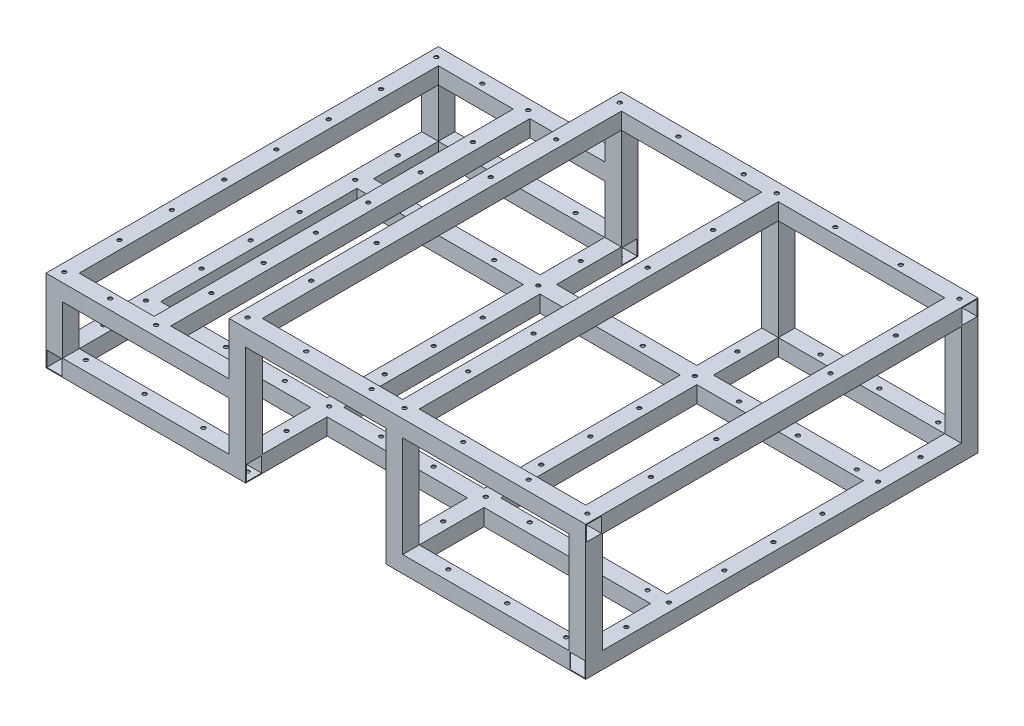
SolidWorks part; units mm, degrees
ref_plane "Front Plane" through (0, 0, 0) normal (0, 0, 1) x (1, 0, 0)
ref_plane "Top Plane" through (0, 0, 0) normal (0, 1, 0) x (1, 0, 0)
ref_plane "Right Plane" through (0, 0, 0) normal (1, 0, 0) x (0, 0, -1)
sketch "Sketch1" plane through (0, 0, 0) normal (0, 1, 0) x (1, 0, 0)
  line L0 (0, 0) -> (-415.7612, 0) construction
  line L1 (-387.3, -150) -> (387.3, -150)
  line L2 (-387.3, -150) -> (-387.3, -175.4)
  line L3 (-387.3, -175.4) -> (387.3, -175.4)
  line L4 (387.3, -150) -> (387.3, -175.4)
  line L9 (0, 0) -> (0, -321.173) construction
  line L10 (387.3, 150) -> (387.3, 175.4)
  line L11 (-387.3, 175.4) -> (387.3, 175.4)
  line L12 (-387.3, 150) -> (-387.3, 175.4)
  line L13 (-387.3, 150) -> (387.3, 150)
  point P7 (0, -175.4)
  dimension "D1" = 774.6
  dimension "D2" = 25.4
  dimension "D3" = 150
  dimension "D4" = 0
extrude "Boss-Extrude1" add sketch "Sketch1" along normal blind 25.4
sketch "Sketch4" plane through (-387.3, 0, 0) normal (-1, 0, 0) x (0, 0, 1)
  line L0 (-175.4, 25.4) -> (-150, 25.4) construction
  line L1 (-174.2, 24.2) -> (-151.2, 24.2)
  line L2 (-174.2, 24.2) -> (-174.2, 1.2)
  line L3 (-174.2, 1.2) -> (-151.2, 1.2)
  line L4 (-151.2, 24.2) -> (-151.2, 1.2)
  line L5 (-150, 25.4) -> (-150, 0) construction
  line L6 (-175.4, 0) -> (-150, 0) construction
  line L7 (-175.4, 25.4) -> (-175.4, 0) construction
  line L8 (0, 0) -> (0, 21.4103) construction
  line L9 (174.2, 1.2) -> (151.2, 1.2)
  line L10 (151.2, 24.2) -> (151.2, 1.2)
  line L11 (174.2, 24.2) -> (151.2, 24.2)
  line L12 (174.2, 24.2) -> (174.2, 1.2)
  dimension "D1" = 1.2
  dimension "D2" = 1.2
  dimension "D3" = 1.2
  dimension "D4" = 1.2
extrude "Cut-Extrude2" cut sketch "Sketch4" against normal up to next (774.6 mm away)
sketch "Sketch2" plane through (0, 0, 0) normal (0, -1, 0) x (1, 0, 0)
  line L0 (0, 0) -> (0, -349.2287) construction
  line L1 (412.7, 300) -> (387.3, 300)
  line L2 (412.7, 300) -> (412.7, -300)
  line L3 (412.7, -300) -> (387.3, -300)
  line L4 (387.3, 300) -> (387.3, -300)
  line L5 (0, 0) -> (432.1136, 0) construction
  line L6 (387.3, -150) -> (387.3, -175.4) construction
  line L7 (-387.3, 300) -> (-387.3, -300)
  line L8 (-412.7, -300) -> (-387.3, -300)
  line L9 (-412.7, 300) -> (-412.7, -300)
  line L10 (-412.7, 300) -> (-387.3, 300)
  point P10 (387.3, 0)
  dimension "D1" = 25.4
  dimension "D2" = 600
  dimension "D3" = 25.4
  dimension "D4" = 0
extrude "Boss-Extrude2" add sketch "Sketch2" against normal blind 25.4
sketch "Sketch3" plane through (0, 0, -300) normal (0, 0, -1) x (-1, 0, 0)
  line L0 (-387.3, 25.4) -> (-412.7, 25.4) construction
  line L1 (-411.5, 24.2) -> (-388.5, 24.2)
  line L2 (-411.5, 24.2) -> (-411.5, 1.2)
  line L3 (-411.5, 1.2) -> (-388.5, 1.2)
  line L4 (-388.5, 24.2) -> (-388.5, 1.2)
  line L5 (-387.3, 25.4) -> (-387.3, 0) construction
  line L6 (-387.3, 0) -> (-412.7, 0) construction
  line L7 (-412.7, 25.4) -> (-412.7, 0) construction
  line L8 (0, 0) -> (0, 119.739) construction
  line L9 (388.5, 24.2) -> (388.5, 1.2)
  line L10 (411.5, 1.2) -> (388.5, 1.2)
  line L11 (411.5, 24.2) -> (411.5, 1.2)
  line L12 (411.5, 24.2) -> (388.5, 24.2)
  point P10 (-400, 0)
  dimension "D1" = 1.2
  dimension "D2" = 1.2
  dimension "D3" = 1.2
  dimension "D4" = 1.2
extrude "Cut-Extrude1" cut sketch "Sketch3" against normal up to next
sketch "Sketch6" plane through (-387.3, 0, 0) normal (1, 0, 0) x (0, 0, -1)
  line L0 (300, 0) -> (175.4, 0) construction
  line L1 (300, 25.4) -> (274.6, 25.4)
  line L2 (300, 25.4) -> (300, 0)
  line L3 (300, 0) -> (274.6, 0)
  line L4 (274.6, 25.4) -> (274.6, 0)
  line L5 (0, 0) -> (0, 25.4) construction
  line L6 (150, 0) -> (-150, 0) construction
  line L7 (150, 25.4) -> (-150, 25.4) construction
  line L13 (-274.6, 25.4) -> (-274.6, 0)
  line L14 (-300, 0) -> (-274.6, 0)
  line L15 (-300, 25.4) -> (-300, 0)
  line L16 (-300, 25.4) -> (-274.6, 25.4)
  dimension "D1" = 25.4
extrude "Boss-Extrude3" add sketch "Sketch6" along normal blind 280
sketch "Sketch7" plane through (387.3, 0, 0) normal (-1, 0, 0) x (0, 0, 1)
  line L0 (-175.4, 25.4) -> (-300, 25.4) construction
  line L1 (-300, 0) -> (-274.6, 0)
  line L2 (-300, 0) -> (-300, 25.4)
  line L3 (-300, 25.4) -> (-274.6, 25.4)
  line L4 (-274.6, 0) -> (-274.6, 25.4)
  line L10 (0, 0) -> (0, 25.4) construction
  line L11 (150, 0) -> (-150, 0) construction
  line L12 (150, 25.4) -> (-150, 25.4) construction
  line L13 (274.6, 0) -> (274.6, 25.4)
  line L14 (300, 25.4) -> (274.6, 25.4)
  line L15 (300, 0) -> (300, 25.4)
  line L16 (300, 0) -> (274.6, 0)
  dimension "D1" = 25.4
extrude "Boss-Extrude4" add sketch "Sketch7" along normal blind 280
ref_plane "Plane1" through (0, 0, 0) normal (1, 0, 0) x (0, 0, -1)
sketch "Sketch8" plane through (0, 0, 0) normal (1, 0, 0) x (0, 0, -1)
  line L4 (-275.8, 24.2) -> (-298.8, 24.2)
  line L5 (-298.8, 24.2) -> (-298.8, 1.2)
  line L6 (-298.8, 1.2) -> (-275.8, 1.2)
  line L7 (-275.8, 1.2) -> (-275.8, 24.2)
  line L8 (-274.6, 25.4) -> (-300, 25.4)
  line L9 (-300, 25.4) -> (-300, 0)
  line L10 (-300, 0) -> (-274.6, 0)
  line L11 (-274.6, 0) -> (-274.6, 25.4)
  line L12 (-274.6, 25.4) -> (-300, 25.4)
  line L13 (-300, 25.4) -> (-300, 0)
  line L14 (-300, 0) -> (-274.6, 0)
  line L15 (-274.6, 0) -> (-274.6, 25.4)
  line L16 (300, 0) -> (300, 25.4)
  line L17 (300, 25.4) -> (274.6, 25.4)
  line L18 (274.6, 25.4) -> (274.6, 0)
  line L19 (274.6, 0) -> (300, 0)
  line L20 (300, 0) -> (300, 25.4)
  line L21 (300, 25.4) -> (274.6, 25.4)
  line L22 (274.6, 25.4) -> (274.6, 0)
  line L23 (274.6, 0) -> (300, 0)
  line L24 (298.8, 1.2) -> (298.8, 24.2)
  line L25 (298.8, 24.2) -> (275.8, 24.2)
  line L26 (275.8, 24.2) -> (275.8, 1.2)
  line L27 (275.8, 1.2) -> (298.8, 1.2)
  dimension "D1" = 0
  dimension "D2" = 0
  dimension "D3" = 1.2
  dimension "D4" = 1.2
extrude "Cut-Extrude4" cut sketch "Sketch8" against normal up to surface (388.5 mm away) and the other way up to vertex (388.5 mm away) contours L24 L25 L26 L27 | L7 L4 L5 L6 up to face at (-388.5, 12.7, 0) other way up to point (388.5, 1.2, 300)
sketch "Sketch9" plane through (0, 0, -274.6) normal (0, 0, 1) x (1, 0, 0)
  line L0 (-107.3, 25.4) -> (-387.3, 25.4) construction
  line L1 (-107.3, 0) -> (-132.7, 0)
  line L2 (-107.3, 0) -> (-107.3, 25.4)
  line L3 (-107.3, 25.4) -> (-132.7, 25.4)
  line L4 (-132.7, 0) -> (-132.7, 25.4)
  line L5 (-107.3, 0) -> (107.3, 0) construction
  line L6 (-107.3, 25.4) -> (107.3, 25.4) construction
  line L7 (0, 25.4) -> (0, 0) construction
  line L12 (-108.5, 1.2) -> (-131.5, 1.2)
  line L13 (-131.5, 1.2) -> (-131.5, 24.2)
  line L14 (-108.5, 24.2) -> (-131.5, 24.2)
  line L15 (-108.5, 1.2) -> (-108.5, 24.2)
  line L16 (108.5, 1.2) -> (108.5, 24.2)
  line L17 (108.5, 24.2) -> (131.5, 24.2)
  line L18 (107.3, 25.4) -> (132.7, 25.4)
  line L19 (107.3, 0) -> (107.3, 25.4)
  line L20 (131.5, 1.2) -> (131.5, 24.2)
  line L21 (108.5, 1.2) -> (131.5, 1.2)
  line L22 (132.7, 0) -> (132.7, 25.4)
  line L23 (107.3, 0) -> (132.7, 0)
  dimension "D1" = 25.4
  dimension "D2" = 1.2
extrude "Boss-Extrude5" add sketch "Sketch9" along normal up to surface (550.4 mm away) up to face at (-247.9, 12.7, 275.8)
sketch "Sketch11" plane through (0, 25.4, 0) normal (0, 1, 0) x (1, 0, 0)
  line L0 (-412.7, 0) -> (0, 0) construction
  line L1 (-412.7, 300) -> (-387.3, 300)
  line L2 (-412.7, 300) -> (-412.7, 274.6)
  line L3 (-412.7, 274.6) -> (-387.3, 274.6)
  line L4 (-387.3, 300) -> (-387.3, 274.6)
  line L5 (-412.7, -300) -> (-412.7, 300) construction
  line L7 (-411.5, 298.8) -> (-388.5, 298.8)
  line L8 (-388.5, 298.8) -> (-388.5, 275.8)
  line L9 (-411.5, 275.8) -> (-388.5, 275.8)
  line L10 (-411.5, 298.8) -> (-411.5, 275.8)
  line L11 (-411.5, -298.8) -> (-411.5, -275.8)
  line L12 (-411.5, -275.8) -> (-388.5, -275.8)
  line L13 (-388.5, -298.8) -> (-388.5, -275.8)
  line L14 (-411.5, -298.8) -> (-388.5, -298.8)
  line L15 (-387.3, -300) -> (-387.3, -274.6)
  line L16 (-412.7, -274.6) -> (-387.3, -274.6)
  line L17 (-412.7, -300) -> (-412.7, -274.6)
  line L18 (-412.7, -300) -> (-387.3, -300)
  dimension "D1" = 1.2
extrude "Boss-Extrude6" add sketch "Sketch11" along normal blind 74.6
sketch "Sketch12" plane through (0, 25.4, 0) normal (0, 1, 0) x (1, 0, 0)
  line L0 (-108.5, 298.8) -> (-131.5, 298.8)
  line L1 (-107.3, 300) -> (-132.7, 300)
  line L2 (-107.3, 300) -> (-107.3, 274.6)
  line L3 (-107.3, 274.6) -> (-132.7, 274.6)
  line L4 (-132.7, 300) -> (-132.7, 274.6)
  line L5 (-131.5, 298.8) -> (-131.5, 275.8)
  line L6 (-108.5, 275.8) -> (-131.5, 275.8)
  line L7 (-108.5, 298.8) -> (-108.5, 275.8)
  line L8 (-132.7, 0) -> (412.7, 0) construction
  line L10 (-132.7, -150) -> (-132.7, 150) construction
  line L11 (412.7, 300) -> (412.7, -300) construction
  line L12 (140, 0) -> (140, 300) construction
  line L13 (107.3, 300) -> (412.7, 300) construction
  line L14 (-108.5, -298.8) -> (-108.5, -275.8)
  line L15 (-108.5, -275.8) -> (-131.5, -275.8)
  line L16 (-131.5, -298.8) -> (-131.5, -275.8)
  line L17 (-132.7, -300) -> (-132.7, -274.6)
  line L18 (-107.3, -274.6) -> (-132.7, -274.6)
  line L19 (-107.3, -300) -> (-107.3, -274.6)
  line L20 (-107.3, -300) -> (-132.7, -300)
  line L21 (-108.5, -298.8) -> (-131.5, -298.8)
  line L22 (388.5, -298.8) -> (411.5, -298.8)
  line L23 (387.3, -300) -> (412.7, -300)
  line L24 (387.3, -300) -> (387.3, -274.6)
  line L25 (387.3, -274.6) -> (412.7, -274.6)
  line L26 (412.7, -300) -> (412.7, -274.6)
  line L27 (411.5, -298.8) -> (411.5, -275.8)
  line L28 (388.5, -275.8) -> (411.5, -275.8)
  line L29 (388.5, -298.8) -> (388.5, -275.8)
  line L30 (388.5, 298.8) -> (388.5, 275.8)
  line L31 (388.5, 275.8) -> (411.5, 275.8)
  line L32 (411.5, 298.8) -> (411.5, 275.8)
  line L33 (412.7, 300) -> (412.7, 274.6)
  line L34 (387.3, 274.6) -> (412.7, 274.6)
  line L35 (387.3, 300) -> (387.3, 274.6)
  line L36 (387.3, 300) -> (412.7, 300)
  line L37 (388.5, 298.8) -> (411.5, 298.8)
  line L38 (132.7, 274.6) -> (387.3, 274.6) construction
  line L39 (107.3, 300) -> (132.7, 300)
  line L40 (107.3, 300) -> (107.3, 274.6)
  line L41 (107.3, 274.6) -> (132.7, 274.6)
  line L42 (132.7, 300) -> (132.7, 274.6)
  line L47 (108.5, 298.8) -> (131.5, 298.8)
  line L48 (131.5, 298.8) -> (131.5, 275.8)
  line L49 (108.5, 275.8) -> (131.5, 275.8)
  line L50 (108.5, 298.8) -> (108.5, 275.8)
  line L51 (108.5, -298.8) -> (108.5, -275.8)
  line L52 (108.5, -275.8) -> (131.5, -275.8)
  line L53 (131.5, -298.8) -> (131.5, -275.8)
  line L54 (108.5, -298.8) -> (131.5, -298.8)
  line L55 (132.7, -300) -> (132.7, -274.6)
  line L56 (107.3, -274.6) -> (132.7, -274.6)
  line L57 (107.3, -300) -> (107.3, -274.6)
  line L58 (107.3, -300) -> (132.7, -300)
  line L59 (107.3, 175.4) -> (107.3, 300) construction
  point P12 (387.3, 287.3)
  dimension "D2" = 0
  dimension "D3" = 25.4
  dimension "D5" = 254.6
  dimension "D6" = 214.6
  dimension "D1" = 1.2
  dimension "D4" = 1.2
extrude "Boss-Extrude7" add sketch "Sketch12" along normal blind 154.6
sketch "Sketch13" plane through (0, 180, 0) normal (0, 1, 0) x (1, 0, 0)
  line L0 (-107.3, 274.6) -> (-107.3, -274.6) construction
  line L1 (-132.7, -300) -> (412.7, -300)
  line L2 (-132.7, -300) -> (-132.7, -274.6)
  line L3 (-132.7, -274.6) -> (412.7, -274.6)
  line L4 (412.7, -300) -> (412.7, -274.6)
  line L5 (-107.3, 0) -> (0, 0) construction
  line L6 (412.7, 300) -> (412.7, 274.6)
  line L7 (-132.7, 274.6) -> (412.7, 274.6)
  line L8 (-132.7, 300) -> (-132.7, 274.6)
  line L9 (-132.7, 300) -> (412.7, 300)
extrude "Boss-Extrude9" add sketch "Sketch13" along normal blind 25.4
sketch "Sketch14" plane through (-132.7, 0, 0) normal (-1, 0, 0) x (0, 0, 1)
  line L0 (-300, 205.4) -> (-274.6, 205.4) construction
  line L1 (-298.8, 204.2) -> (-275.8, 204.2)
  line L2 (-298.8, 204.2) -> (-298.8, 181.2)
  line L3 (-298.8, 181.2) -> (-275.8, 181.2)
  line L4 (-275.8, 204.2) -> (-275.8, 181.2)
  line L5 (-300, 205.4) -> (-300, 25.4) construction
  line L6 (-274.6, 205.4) -> (-274.6, 25.4) construction
  line L7 (-300, 180) -> (-274.6, 180) construction
  line L8 (-274.6, 180) -> (274.6, 180) construction
  line L9 (274.6, 205.4) -> (274.6, 25.4) construction
  line L10 (0, 180) -> (0, 204.2) construction
  line L11 (300, 180) -> (274.6, 180) construction
  line L12 (275.8, 204.2) -> (275.8, 181.2)
  line L13 (298.8, 181.2) -> (275.8, 181.2)
  line L14 (298.8, 204.2) -> (298.8, 181.2)
  line L15 (298.8, 204.2) -> (275.8, 204.2)
  dimension "D1" = 1.2
  dimension "D2" = 1.2
  dimension "D3" = 1.2
  dimension "D4" = 25.4
  dimension "D5" = 1.2
extrude "Cut-Extrude5" cut sketch "Sketch14" against normal up to surface (545.4 mm away) up to face at (412.7, 109.05, 0)
sketch "Sketch15" plane through (0, 0, -274.6) normal (0, 0, 1) x (1, 0, 0)
  line L27 (107.3, 180) -> (132.7, 180)
  line L28 (132.7, 180) -> (132.7, 205.4)
  line L29 (-132.7, 205.4) -> (412.7, 205.4) construction
  line L30 (132.7, 205.4) -> (107.3, 205.4)
  line L31 (107.3, 205.4) -> (107.3, 180)
  line L32 (108.5, 181.2) -> (131.5, 181.2)
  line L33 (131.5, 181.2) -> (131.5, 204.2)
  line L34 (131.5, 204.2) -> (108.5, 204.2)
  line L35 (108.5, 204.2) -> (108.5, 181.2)
  line L36 (-107.3, 180) -> (-107.3, 25.4) construction
  line L37 (-132.7, 205.4) -> (-107.3, 205.4)
  line L38 (-132.7, 205.4) -> (-132.7, 180)
  line L39 (-132.7, 180) -> (-107.3, 180)
  line L40 (-107.3, 205.4) -> (-107.3, 180)
  line L41 (-131.5, 204.2) -> (-108.5, 204.2)
  line L42 (412.7, 205.4) -> (387.3, 205.4)
  line L43 (412.7, 205.4) -> (412.7, 180)
  line L44 (412.7, 180) -> (387.3, 180)
  line L45 (387.3, 205.4) -> (387.3, 180)
  line L46 (-108.5, 204.2) -> (-108.5, 181.2)
  line L47 (-131.5, 181.2) -> (-108.5, 181.2)
  line L48 (-131.5, 204.2) -> (-131.5, 181.2)
  line L49 (411.5, 204.2) -> (388.5, 204.2)
  line L50 (388.5, 204.2) -> (388.5, 181.2)
  line L51 (411.5, 181.2) -> (388.5, 181.2)
  line L52 (411.5, 204.2) -> (411.5, 181.2)
  dimension "D2" = 1.2
  dimension "D1" = 1.2
extrude "Boss-Extrude10" add sketch "Sketch15" along normal up to surface (549.2 mm away) up to face at (260, 12.7, 274.6)
sketch "Sketch16" plane through (-412.7, 0, 0) normal (-1, 0, 0) x (0, 0, 1)
  line L0 (275.8, 101.2) -> (298.8, 101.2)
  line L1 (274.6, 100) -> (300, 100)
  line L2 (274.6, 100) -> (274.6, 125.4)
  line L3 (274.6, 125.4) -> (300, 125.4)
  line L4 (300, 100) -> (300, 125.4)
  line L5 (298.8, 101.2) -> (298.8, 124.2)
  line L6 (275.8, 124.2) -> (298.8, 124.2)
  line L7 (275.8, 101.2) -> (275.8, 124.2)
  line L8 (-274.6, 100) -> (274.6, 100) construction
  line L9 (0, 100) -> (0, 0) construction
  line L11 (300, 0) -> (-300, 0) construction
  line L12 (-275.8, 101.2) -> (-275.8, 124.2)
  line L13 (-275.8, 124.2) -> (-298.8, 124.2)
  line L14 (-298.8, 101.2) -> (-298.8, 124.2)
  line L15 (-300, 100) -> (-300, 125.4)
  line L16 (-274.6, 125.4) -> (-300, 125.4)
  line L17 (-274.6, 100) -> (-274.6, 125.4)
  line L18 (-274.6, 100) -> (-300, 100)
  line L19 (-275.8, 101.2) -> (-298.8, 101.2)
  dimension "D1" = 25.4
  dimension "D2" = 25.4
  dimension "D3" = 1.2
extrude "Boss-Extrude11" add sketch "Sketch16" against normal up to surface (280 mm away) up to face at (-132.7, 192.7, -287.3)
sketch "Sketch17" plane through (0, 0, 274.6) normal (0, 0, -1) x (-1, 0, 0)
  line L0 (132.7, 100) -> (387.3, 100) construction
  line L1 (387.3, 100) -> (412.7, 100)
  line L2 (387.3, 100) -> (387.3, 125.4)
  line L3 (387.3, 125.4) -> (412.7, 125.4)
  line L4 (412.7, 100) -> (412.7, 125.4)
  line L5 (260, 100) -> (260, 125.4) construction
  line L6 (132.7, 125.4) -> (412.7, 125.4) construction
  line L7 (248.5, 124.2) -> (271.5, 124.2)
  line L8 (247.3, 125.4) -> (272.7, 125.4)
  line L9 (247.3, 125.4) -> (247.3, 100)
  line L10 (247.3, 100) -> (272.7, 100)
  line L11 (272.7, 125.4) -> (272.7, 100)
  line L12 (271.5, 124.2) -> (271.5, 101.2)
  line L13 (248.5, 101.2) -> (271.5, 101.2)
  line L14 (248.5, 124.2) -> (248.5, 101.2)
  line L16 (388.5, 101.2) -> (411.5, 101.2)
  line L17 (411.5, 101.2) -> (411.5, 124.2)
  line L18 (388.5, 124.2) -> (411.5, 124.2)
  line L19 (388.5, 101.2) -> (388.5, 124.2)
  dimension "D1" = 25.4
  dimension "D2" = 12.7
  dimension "D3" = 1.2
  dimension "D4" = 1.2
extrude "Boss-Extrude12" add sketch "Sketch17" along normal up to surface (549.2 mm away) up to face at (260, 12.7, -274.6)
sketch "Sketch18" plane through (0, 25.4, 0) normal (0, 1, 0) x (1, 0, 0)
  line L0 (132.7, 274.6) -> (387.3, 274.6) construction
  line L1 (387.3, 300) -> (387.3, 274.6) construction
  line L2 (132.7, 274.6) -> (387.3, 274.6) construction
  line L3 (107.3, 175.4) -> (107.3, 274.6) construction
  line L4 (387.3, -150) -> (387.3, 150) construction
  line L5 (132.7, 150) -> (387.3, 150) construction
  line L6 (107.3, -150) -> (107.3, 150) construction
  line L7 (412.7, 0) -> (0, 0) construction
  line L8 (412.7, 274.6) -> (412.7, -274.6) construction
  line L9 (0, 0) -> (0, 303.2716) construction
  line L11 (387.3, 175.4) -> (387.3, 274.6) construction
  line L12 (388.5, 300) -> (411.5, 300) construction
  line L13 (411.5, 300) -> (388.5, 300) construction
  line L14 (107.3, 300) -> (412.7, 300) construction
  line L15 (-107.3, 150) -> (107.3, 150) construction
  line L16 (132.7, 300) -> (387.3, 300) construction
  circle A0 centre (367.3, 284.6) radius 3
  circle A1 centre (277.3, 284.6) radius 3
  circle A2 centre (187.3, 284.6) radius 3
  circle A3 centre (119.8, 284.6) radius 3
  circle A4 centre (367.3, 160) radius 3
  circle A5 centre (277.3, 160) radius 3
  circle A6 centre (187.3, 160) radius 3
  circle A7 centre (119.8, 160) radius 3
  circle A8 centre (119.8, 225) radius 3
  circle A9 centre (399.8, 225) radius 3
  circle A11 centre (399.8, 0) radius 3
  circle A12 centre (399.8, 75) radius 3
  circle A13 centre (119.8, 0) radius 3
  circle A14 centre (119.8, 75) radius 3
  circle A15 centre (399.8, 160) radius 3
  circle A16 centre (40, 160) radius 3
  circle A17 centre (-40, 160) radius 3
  circle A18 centre (-399.8, 160) radius 3
  circle A19 centre (-119.8, 75) radius 3
  circle A20 centre (-119.8, 0) radius 3
  circle A21 centre (-399.8, 75) radius 3
  circle A22 centre (-399.8, 0) radius 3
  circle A23 centre (-399.8, 225) radius 3
  circle A24 centre (-119.8, 225) radius 3
  circle A25 centre (-119.8, 160) radius 3
  circle A26 centre (-187.3, 160) radius 3
  circle A27 centre (-277.3, 160) radius 3
  circle A28 centre (-367.3, 160) radius 3
  circle A29 centre (-119.8, 284.6) radius 3
  circle A30 centre (-187.3, 284.6) radius 3
  circle A31 centre (-277.3, 284.6) radius 3
  circle A32 centre (-367.3, 284.6) radius 3
  circle A33 centre (-367.3, -284.6) radius 3
  circle A34 centre (-277.3, -284.6) radius 3
  circle A35 centre (-187.3, -284.6) radius 3
  circle A36 centre (-119.8, -284.6) radius 3
  circle A37 centre (-367.3, -160) radius 3
  circle A38 centre (-277.3, -160) radius 3
  circle A39 centre (-187.3, -160) radius 3
  circle A40 centre (-119.8, -160) radius 3
  circle A41 centre (-119.8, -225) radius 3
  circle A42 centre (-399.8, -225) radius 3
  circle A43 centre (-399.8, -75) radius 3
  circle A44 centre (-119.8, -75) radius 3
  circle A45 centre (-399.8, -160) radius 3
  circle A46 centre (-40, -160) radius 3
  circle A47 centre (40, -160) radius 3
  circle A48 centre (399.8, -160) radius 3
  circle A49 centre (119.8, -75) radius 3
  circle A50 centre (399.8, -75) radius 3
  circle A51 centre (399.8, -225) radius 3
  circle A52 centre (119.8, -225) radius 3
  circle A53 centre (119.8, -160) radius 3
  circle A54 centre (187.3, -160) radius 3
  circle A55 centre (277.3, -160) radius 3
  circle A56 centre (367.3, -160) radius 3
  circle A57 centre (119.8, -284.6) radius 3
  circle A58 centre (187.3, -284.6) radius 3
  circle A59 centre (277.3, -284.6) radius 3
  circle A60 centre (367.3, -284.6) radius 3
  dimension "D1" = 10
  dimension "D5" = 6
  dimension "D6" = 6
  dimension "D7" = 10
  dimension "D9" = 6
  dimension "D10" = 6
  dimension "D13" = 6
  dimension "D14" = 6
  dimension "D15" = 6
  dimension "D22" = 6
  dimension "D27" = 6
  dimension "D28" = 6
  dimension "D29" = 12.5
  dimension "D30" = 75
  dimension "D33" = 6
  dimension "D34" = 6
  dimension "D35" = 6
  dimension "D36" = 6
  dimension "D43" = 6
  dimension "D44" = 12.5
  dimension "D46" = 6
  dimension "D2" = 20
  dimension "D3" = 10
  dimension "D4" = 110
  dimension "D8" = 200
  dimension "D11" = 10
  dimension "D12" = 12.5
  dimension "D16" = 20
  dimension "D17" = 10
  dimension "D18" = 110
  dimension "D19" = 10
  dimension "D20" = 10
  dimension "D21" = 200
  dimension "D23" = 10
  dimension "D24" = 12.5
  dimension "D25" = 12.5
  dimension "D26" = 75
  dimension "D31" = 12.5
  dimension "D32" = 300
  dimension "D37" = 12.5
  dimension "D38" = 12.5
  dimension "D39" = 225
  dimension "D40" = 300
  dimension "D41" = 225
  dimension "D42" = 12.5
  dimension "D45" = 10
  dimension "D47" = 10
  dimension "D48" = 40
extrude "Cut-Extrude6" cut sketch "Sketch18" against normal up to surface (25.4 mm away) up to face at (0, 0, 0)
sketch "Sketch20" plane through (0, 205.4, 0) normal (0, 1, 0) x (1, 0, 0)
  line L0 (387.3, 0) -> (132.7, 0) construction
  line L1 (387.3, -274.6) -> (387.3, 274.6) construction
  line L2 (132.7, -274.6) -> (132.7, 274.6) construction
  line L3 (412.7, 300) -> (-132.7, 300) construction
  line L4 (140, 300) -> (140, -300) construction
  line L5 (-132.7, -300) -> (412.7, -300) construction
  line L6 (260, 274.6) -> (260, 0) construction
  line L7 (132.7, 274.6) -> (387.3, 274.6) construction
  line L8 (260, 137.3) -> (387.3, 137.3) construction
  line L9 (387.3, -274.6) -> (387.3, 274.6) construction
  circle A0 centre (399.8, 284.6) radius 3
  circle A2 centre (399.8, 187.3) radius 3
  circle A3 centre (310, 284.6) radius 3
  circle A4 centre (210, 284.6) radius 3
  circle A5 centre (120.2, 187.3) radius 3
  circle A6 centre (120.2, 284.6) radius 3
  circle A7 centre (120.2, 87.3) radius 3
  circle A8 centre (399.8, 87.3) radius 3
  circle A9 centre (399.8, -87.3) radius 3
  circle A10 centre (120.2, -87.3) radius 3
  circle A11 centre (120.2, -284.6) radius 3
  circle A12 centre (120.2, -187.3) radius 3
  circle A13 centre (210, -284.6) radius 3
  circle A14 centre (310, -284.6) radius 3
  circle A15 centre (399.8, -187.3) radius 3
  circle A16 centre (399.8, -284.6) radius 3
  circle A17 centre (-119.8, -284.6) radius 3
  circle A18 centre (-119.8, -187.3) radius 3
  circle A19 centre (-30, -284.6) radius 3
  circle A20 centre (70, -284.6) radius 3
  circle A21 centre (-119.8, -87.3) radius 3
  circle A22 centre (-119.8, 87.3) radius 3
  circle A23 centre (70, 284.6) radius 3
  circle A24 centre (-30, 284.6) radius 3
  circle A25 centre (-119.8, 187.3) radius 3
  circle A26 centre (-119.8, 284.6) radius 3
  dimension "D1" = 6
  dimension "D6" = 6
  dimension "D7" = 6
  dimension "D2" = 10
  dimension "D3" = 12.5
  dimension "D4" = 10
  dimension "D5" = 50
  dimension "D8" = 50
  dimension "D9" = 12.5
extrude "Cut-Extrude7" cut sketch "Sketch20" against normal up to next (1.2 mm away)
sketch "Sketch21" plane through (0, 125.4, 0) normal (0, 1, 0) x (1, 0, 0)
  line L0 (-272.7, 0) -> (-387.3, 0) construction
  line L1 (-272.7, 274.6) -> (-272.7, -274.6) construction
  line L2 (-387.3, 274.6) -> (-387.3, -274.6) construction
  line L3 (-330, 274.6) -> (-330, 0) construction
  line L4 (-272.7, 274.6) -> (-387.3, 274.6) construction
  line L5 (-412.7, -300) -> (-412.7, 300) construction
  line L6 (-132.7, 300) -> (-412.7, 300) construction
  circle A0 centre (-400.2, 284.6) radius 3
  circle A1 centre (-329.995, 284.6) radius 3
  circle A2 centre (-400.2, 200) radius 3
  circle A3 centre (-400.2, 120) radius 3
  circle A4 centre (-400.2, 40) radius 3
  circle A5 centre (-259.8, 40) radius 3
  circle A6 centre (-259.8, 120) radius 3
  circle A7 centre (-259.8, 200) radius 3
  circle A8 centre (-259.8, 284.6) radius 3
  circle A9 centre (-259.8, -284.6) radius 3
  circle A10 centre (-259.8, -200) radius 3
  circle A11 centre (-259.8, -120) radius 3
  circle A12 centre (-400.2, -40) radius 3
  circle A13 centre (-400.2, -120) radius 3
  circle A14 centre (-400.2, -200) radius 3
  circle A15 centre (-329.995, -284.6) radius 3
  circle A16 centre (-400.2, -284.6) radius 3
  circle A17 centre (-259.8, -40) radius 3
  dimension "D1" = 12.5
  dimension "D3" = 6
  dimension "D4" = 6
  dimension "D5" = 10
  dimension "D8" = 6
  dimension "D9" = 6
  dimension "D13" = 12.5
  dimension "D14" = 6
  dimension "D2" = 10
  dimension "D6" = 0.01
  dimension "D7" = 12.5
  dimension "D10" = 12.5
  dimension "D11" = 100
  dimension "D12" = 120
  dimension "D15" = 40
extrude "Cut-Extrude8" cut sketch "Sketch21" against normal up to next
equation "\"thi\"=1.2"
equation "\"D5@Sketch14\"=\"thi\""
equation "\"D2@Sketch14\"=\"thi\""
equation "\"D3@Sketch14\"=\"thi\""
equation "\"D1@Sketch14\"=\"thi\""
